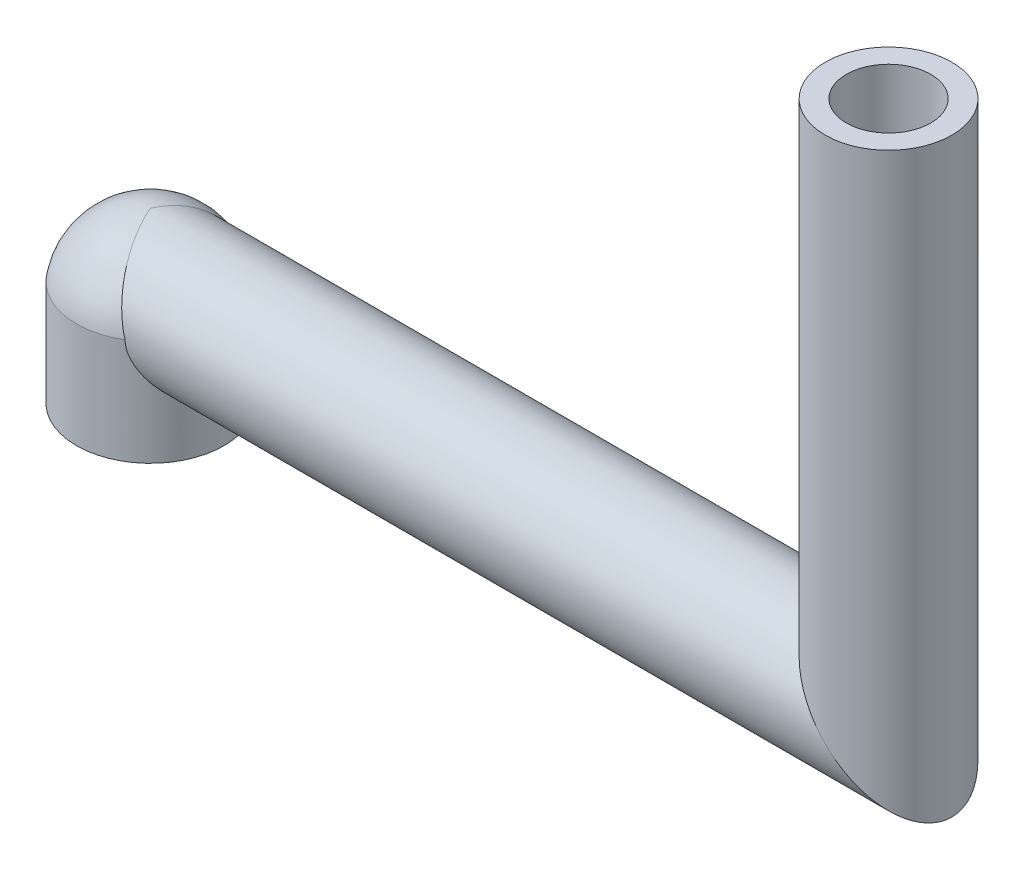
SolidWorks part; units mm, degrees
ref_plane "Front Plane" through (0, 0, 0) normal (0, 0, 1) x (1, 0, 0)
ref_plane "Top Plane" through (0, 0, 0) normal (0, 1, 0) x (1, 0, 0)
ref_plane "Right Plane" through (0, 0, 0) normal (1, 0, 0) x (0, 0, -1)
sketch "Sketch1" plane through (0, 0, 0) normal (0, 1, 0) x (1, 0, 0)
  circle A0 centre (0, 0) radius 6
  circle A1 centre (0, 0) radius 7
  dimension "D1" = 12
  dimension "D2" = 14
extrude "Boss-Extrude1" add sketch "Sketch1" along normal blind 10
sketch "Sketch2" plane through (0, 0, 0) normal (0, 0, 1) x (1, 0, 0)
  line L0 (0, 10) -> (7, 10)
  line L1 (7, 10) -> (-7, 10) construction
  line L2 (0, 16) -> (0, 10)
  arc A0 (0, 16) -> (7, 10) centre (0, 8.9167) cw
  dimension "D1" = 6
revolve "Revolve1" add sketch "Sketch2" angle 360 about L2
sketch "Sketch3" plane through (0, 0, 0) normal (0, 0, 1) x (1, 0, 0)
  line L0 (7, 10) -> (-7, 10) construction
  line L9 (70, 60) -> (70, 10)
  line L10 (70, 10) -> (0, 10)
  dimension "D1" = 70
  dimension "D3" = 50
ref_plane "Plane1" through (0, 60, 0) normal (0, 1, 0) x (1, 0, 0)
sketch "Sketch4" plane through (0, 60, 0) normal (0, 1, 0) x (1, 0, 0)
  circle A0 centre (70, 0) radius 6
  dimension "D1" = 12
sweep "Sweep2" add profiles "Sketch4" path "Sketch3"
sketch "Sketch5" plane through (0, 0, 0) normal (0, -1, 0) x (1, 0, 0)
  circle A0 centre (0, 0) radius 6
  dimension "D1" = 12
extrude "Cut-Extrude1" cut sketch "Sketch5" against normal up to surface (10 mm away) up to face at (-3, 10, 0)
shell "Shell1" thickness 2 removed face at (70, 60, 6)
